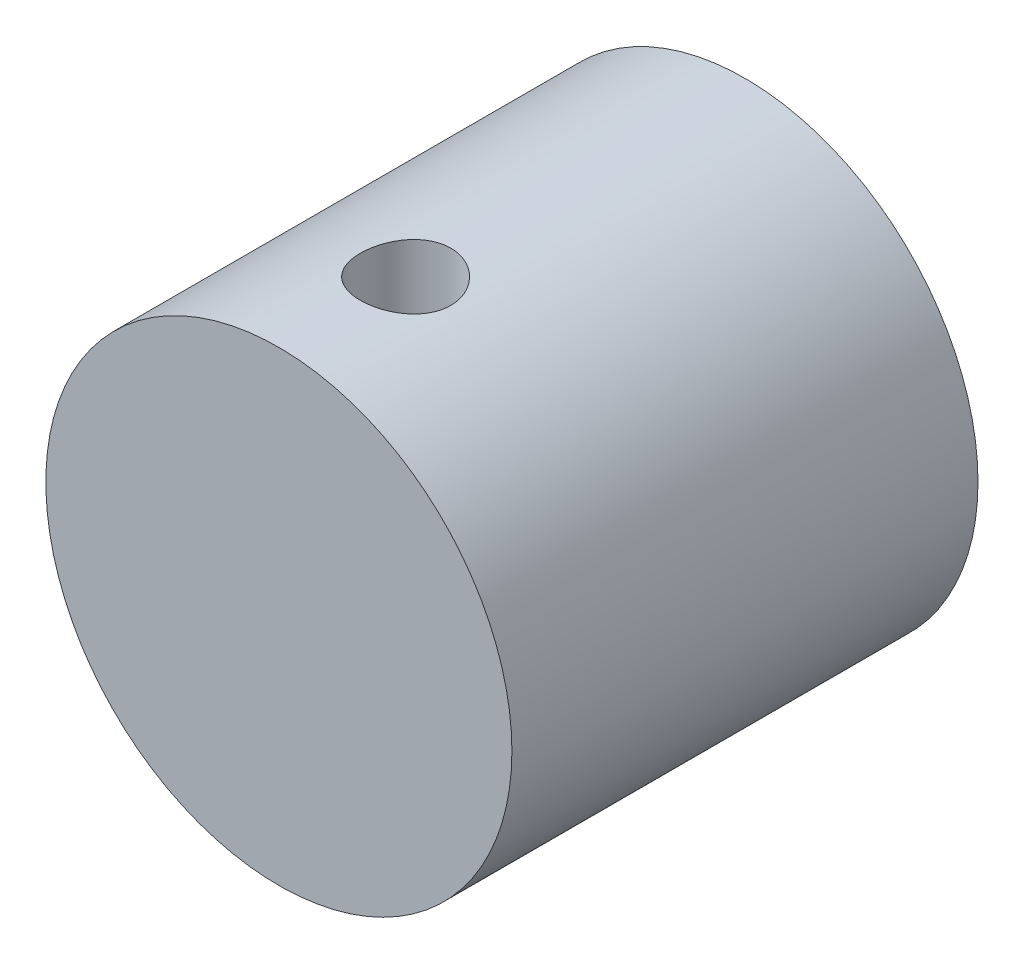
SolidWorks part; units mm, degrees
material "ABS"
ref_plane "Front Plane" through (0, 0, 0) normal (0, 0, 1) x (1, 0, 0)
ref_plane "Top Plane" through (0, 0, 0) normal (0, 1, 0) x (1, 0, 0)
ref_plane "Right Plane" through (0, 0, 0) normal (1, 0, 0) x (0, 0, -1)
sketch "Sketch1" plane through (0, 0, 0) normal (0, 0, 1) x (1, 0, 0)
  circle A0 centre (0, 0) radius 5.15
  dimension "D1" = 10.3
extrude "Boss-Extrude1" add sketch "Sketch1" along normal blind 10.3
sketch "Sketch2" plane through (0, 0, 0) normal (0, 1, 0) x (1, 0, 0)
  line L0 (0, 0) -> (0, -7.5) construction
  circle A0 centre (0, -7.5) radius 1
  dimension "D1" = 2
  dimension "D2" = 7.5
extrude "Cut-Extrude1" cut sketch "Sketch2" against normal blind 10 and the other way blind 10
sketch "Sketch3" plane through (0, 0, 0) normal (0, 0, -1) x (-1, 0, 0)
  line L1 (-2.025, 2.025) -> (2.025, 2.025)
  line L2 (-2.025, 2.025) -> (-2.025, -2.025)
  line L3 (-2.025, -2.025) -> (2.025, -2.025)
  line L4 (2.025, 2.025) -> (2.025, -2.025)
  line L5 (-2.025, 2.025) -> (2.025, -2.025) construction
  line L6 (-2.025, -2.025) -> (2.025, 2.025) construction
  point P0 (0, 0)
  dimension "D1" = 4.05
  dimension "D2" = 4.05
extrude "Cut-Extrude2" cut sketch "Sketch3" against normal blind 5
